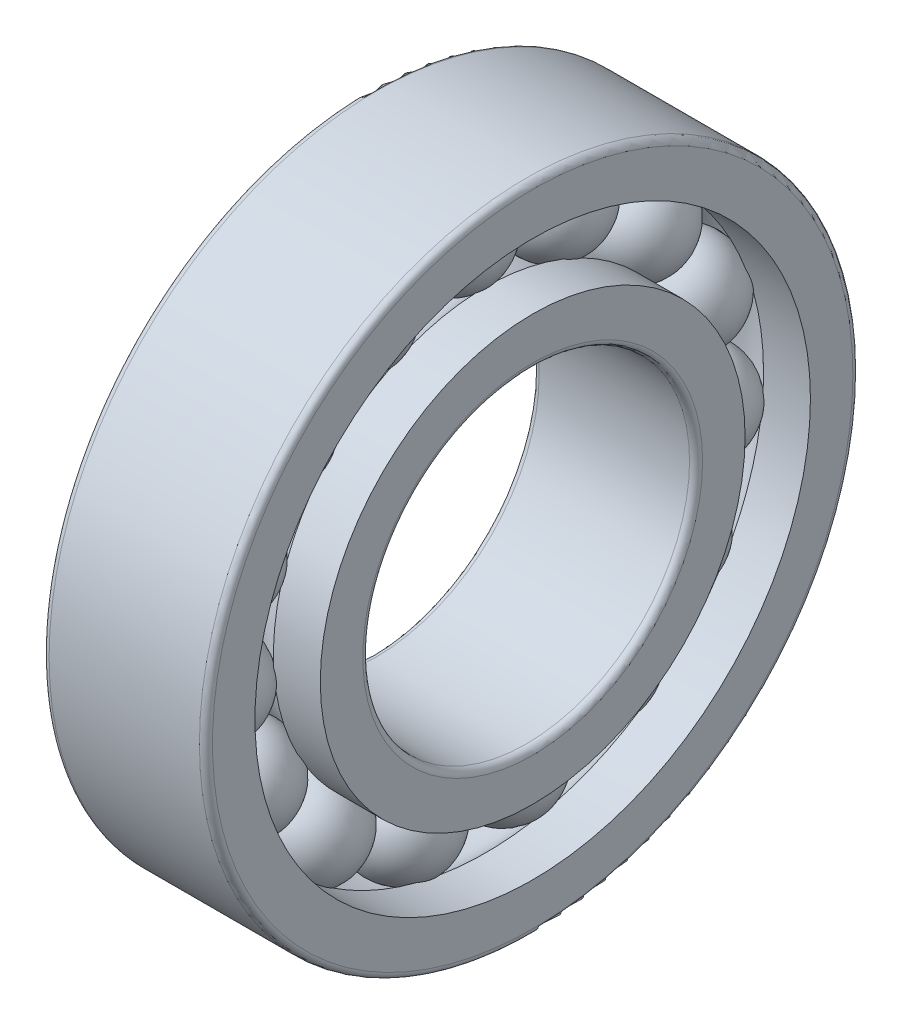
SolidWorks part; units mm, degrees
ref_plane "Plane1" through (0, 0, 0) normal (0, 0, 1) x (1, 0, 0)
ref_plane "Plane2" through (0, 0, 0) normal (0, 1, 0) x (1, 0, 0)
ref_plane "Plane3" through (0, 0, 0) normal (1, 0, 0) x (0, 0, -1)
sketch "Clipboard" plane through (0, 0, 0) normal (0, 0, 1) x (1, 0, 0)
  line L0 (-10, 0) -> (10, 0) construction
  line L1 (0, 0) -> (21.5988, -5.7874)
  line L2 (0, 0) -> (4.7618, -0.0831)
  line L3 (0, 0) -> (22.3573, 0.3902)
  line L4 (0, 0) -> (-22.3573, -0.3902)
sketch "CagSpiSke" plane through (0, 0, 0) normal (0, 0, 1) x (1, 0, 0)
  line L0 (0.0952, 4.6038) -> (0.0953, 4.9213)
  line L1 (0.0953, 4.9213) -> (-0.0953, 4.9213)
  line L2 (-0.0953, 4.9213) -> (-0.0952, 4.6038)
  line L3 (-0.0952, 4.6038) -> (0.0952, 4.6038)
  line L4 (-20.6375, 0) -> (20.6375, 0) construction
  line L5 (0, 0) -> (0, 23.7692) construction
revolve "CageSpine" add sketch "CagSpiSke" angle 0.001 about L4 reverse direction yes
ref_axis "Axis1" through (-50, 0, 0) along (1, 0, 0)
sketch "CagBalSke" plane through (0, 0, 0) normal (0, 0, 1) x (1, 0, 0)
  line L0 (-1.0478, 4.7625) -> (1.0478, 4.7625)
  line L1 (-1.905, 4.7625) -> (1.905, 4.7625) construction
  line L2 (-10, 0) -> (10, 0) construction
  line L3 (0, 0) -> (0, 24) construction
  arc A0 (1.0478, 4.7625) -> (-1.0478, 4.7625) centre (0, 4.7625) cw
revolve "CageBall" [suppressed] add sketch "CagBalSke" angle 360 about L1 reverse direction yes
pattern_circular "CageBalls" [suppressed] count 15 every 24 about axis through (-50, 0, 0) along (1, 0, 0)
sketch "CagTrmODSke" plane through (0, 0, 0) normal (0, 0, 1) x (1, 0, 0)
  line L0 (1.0488, 4.9212) -> (1.0488, 5.8113)
  line L1 (1.0488, 5.8113) -> (-1.0488, 5.8113)
  line L2 (-1.0488, 5.8113) -> (-1.0488, 4.9212)
  line L3 (-1.0488, 4.9212) -> (1.0488, 4.9212)
  line L4 (-20.6375, 0) -> (20.6375, 0) construction
  line L5 (0, 0) -> (0, 25) construction
revolve "CageTrimOD" [suppressed] cut sketch "CagTrmODSke" angle 360 about L4 reverse direction yes
sketch "CagTrmIDSke" plane through (0, 0, 0) normal (0, 0, 1) x (1, 0, 0)
  line L0 (1.0487, 3.7158) -> (1.0488, 4.6037)
  line L1 (1.0488, 4.6037) -> (-1.0488, 4.6037)
  line L2 (-1.0488, 4.6037) -> (-1.0487, 3.7158)
  line L3 (-1.0487, 3.7158) -> (1.0487, 3.7158)
  line L4 (-20.6375, 0) -> (20.6375, 0) construction
  line L5 (0, 0) -> (0, 25) construction
revolve "CageTrimID" [suppressed] cut sketch "CagTrmIDSke" angle 360 about L4 reverse direction yes
sketch "BalSimSke" plane through (0, 0, 0) normal (0, 0, 1) x (1, 0, 0)
  line L0 (-10, 0) -> (10, 0) construction
  line L1 (-10, 4.7625) -> (10, 4.7625) construction
  line L2 (0, 0) -> (0, 23) construction
  circle A0 centre (0, 4.7625) radius 0.9525
revolve "BallsSimplified" [suppressed] add sketch "BalSimSke" angle 360 about L0
sketch "BalDetSke" plane through (0, 0, 0) normal (0, 0, 1) x (1, 0, 0)
  line L0 (-0.9525, 4.7625) -> (0.9525, 4.7625)
  line L1 (-1.905, 4.7625) -> (1.905, 4.7625) construction
  line L2 (0, 0) -> (0, 25) construction
  arc A0 (0.9525, 4.7625) -> (-0.9525, 4.7625) centre (0, 4.7625) cw
revolve "BallDetailed" add sketch "BalDetSke" angle 360 about L1 reverse direction yes
sketch "InnRacSke" plane through (0, 0, 0) normal (0, 0, 1) x (1, 0, 0)
  line L0 (-0.676, 4.1275) -> (-1.5875, 4.1275)
  line L1 (-1.5875, 4.1275) -> (-1.5875, 3.302)
  line L2 (-1.4605, 3.175) -> (1.4605, 3.175)
  line L3 (1.5875, 3.302) -> (1.5875, 4.1275)
  line L4 (1.5875, 4.1275) -> (0.676, 4.1275)
  line L5 (-20.6375, 0) -> (20.6375, 0) construction
  line L6 (0, 0) -> (0, 30) construction
  arc A0 (-1.5875, 3.302) -> (-1.4605, 3.175) centre (-1.4605, 3.302) ccw
  arc A1 (1.4605, 3.175) -> (1.5875, 3.302) centre (1.4605, 3.302) ccw
  arc A2 (0.676, 4.1275) -> (-0.676, 4.1275) centre (0, 4.7625) cw
  dimension "Fillet_radius" = 0.127
  dimension "ID" = 6.35
revolve "InnerRace" add sketch "InnRacSke" angle 360 about L5 reverse direction yes
sketch "OutRacSke" plane through (0, 0, 0) normal (0, 0, 1) x (1, 0, 0)
  line L0 (-0.676, 5.3975) -> (-1.5875, 5.3975)
  line L1 (-1.5875, 5.3975) -> (-1.5875, 6.223)
  line L2 (-1.4605, 6.35) -> (1.4605, 6.35)
  line L3 (1.5875, 6.223) -> (1.5875, 5.3975)
  line L4 (1.5875, 5.3975) -> (0.676, 5.3975)
  line L5 (-20.6375, 0) -> (20.6375, 0) construction
  line L6 (0, 0) -> (0, 30) construction
  arc A0 (-1.5875, 6.223) -> (-1.4605, 6.35) centre (-1.4605, 6.223) cw
  arc A1 (1.4605, 6.35) -> (1.5875, 6.223) centre (1.4605, 6.223) cw
  arc A2 (0.676, 5.3975) -> (-0.676, 5.3975) centre (0, 4.7625) ccw
  dimension "Fillet_radius" = 0.127
revolve "OuterRace" add sketch "OutRacSke" angle 360 about L5 reverse direction yes
pattern_circular "BallsDetailed" count 15 every 24 about axis through (-50, 0, 0) along (1, 0, 0) of "BallDetailed"
equation "\"BallCLRad@Clipboard\" = ( \"OD@OutRacSke\" + \"ID@InnRacSke\" ) / 4"
equation "\"BallCLRad@BalSimSke\" = \"BallCLRad@Clipboard\""
equation "\"BallCLRad@BalDetSke\" = \"BallCLRad@Clipboard\""
equation "\"BallCLRad@InnRacSke\" = \"BallCLRad@Clipboard\""
equation "\"BallCLRad@OutRacSke\" = \"BallCLRad@Clipboard\""
equation "\"Ball_diameter@InnRacSke\" = \"Ball_diameter@BalDetSke\" - 0.05"
equation "\"Ball_diameter@OutRacSke\" = \"Ball_diameter@BalDetSke\" - 0.05"
equation "\"Ball_diameter@BalSimSke\" = \"Ball_diameter@BalDetSke\""
equation "\"Width@OutRacSke\" = \"Width@InnRacSke\""
equation "\"Fillet_radius@OutRacSke\" = \"Fillet_radius@InnRacSke\""
equation "\"Max_count@Clipboard\" = int( 3.14159265 / atn(( \"Ball_diameter@BalDetSke\" / 2) / sqr( \"BallCLRad@Clipboard\"  *  \"BallCLRad@Clipboard\" - ( \"Ball_diameter@BalDetSke\" / 2) *  ( \"Ball_diameter@BalDetSke\" / 2))))"
equation "\"Max_count@Clipboard\" = ((sgn( \"Max_count@Clipboard\" - \"Count@Clipboard\" )-1)*( \"Max_count@Clipboard\" - \"Count@Clipboard\" ))/-2+ \"Count@Clipboard\""
equation "\"Count@BallsDetailed\" = int( \"Show_count@Clipboard\" ) "
equation "\"Count@BallsDetailed\" = ((sgn( \"Count@BallsDetailed\" - \"Max_count@Clipboard\" )-1)*( \"Count@BallsDetailed\" - \"Max_count@Clipboard\" ))/-2+ \"Max_count@Clipboard\""
equation "\"Count@BallsDetailed\" = ((sgn( \"Count@BallsDetailed\" - \"Min_count@Clipboard\" )+1)*( \"Count@BallsDetailed\" - \"Min_count@Clipboard\"))/2 +\"Min_count@Clipboard\""
equation "\"Angle@BallsDetailed\" = 360.0 / \"Max_count@Clipboard\""
equation "\"BallCLRad@CagBalSke\" = \"BallCLRad@Clipboard\""
equation "\"Count@CageBalls\" = \"Count@BallsDetailed\""
equation "\"Angle@CageBalls\" = \"Angle@BallsDetailed\""
equation "\"Angle@CageSpine\" =  \"Angle@CageBalls\" * ( \"Count@CageBalls\" -1 + int( \"Count@CageBalls\" / \"Max_count@Clipboard\" ) )  + 0.001 -  int( \"Count@CageBalls\" / \"Max_count@Clipboard\" ) * 0.001"
equation "\"Angle@CageSpine\" =  \"Angle@CageSpine\" * int( \"Min_count@Clipboard\" / 2) + int(1 / \"Min_count@Clipboard\")  * 0.001"
equation "\"CageWallOD@CagBalSke\" =  \"Ball_diameter@BalDetSke\" * 1.1"
equation "\"Thickness@CagSpiSke\" =  \"Ball_diameter@BalDetSke\" * 0.1"
equation "\"OD@CagTrmODSke\" = \"BallCLRad@Clipboard\" * 2 + \"CageWallOD@CagBalSke\" + 0.002"
equation "\"ID@CagTrmODSke\" = \"BallCLRad@Clipboard\" * 2 + \"Ball_diameter@BalDetSke\" / 6"
equation "\"OD@CagTrmIDSke\" = \"BallCLRad@Clipboard\" * 2 - \"Ball_diameter@BalDetSke\" / 6"
equation "\"ID@CagTrmIDSke\" = \"BallCLRad@Clipboard\" * 2 - \"CageWallOD@CagBalSke\" + 0.002"
equation "\"OD@CagSpiSke\" = \"ID@CagTrmODSke\""
equation "\"ID@CagSpiSke\" = \"OD@CagTrmIDSke\""
equation "\"Width@CagTrmODSke\" = \"CageWallOD@CagBalSke\" + 0.002"
equation "\"Width@CagTrmIDSke\" = \"CageWallOD@CagBalSke\" + 0.002"
